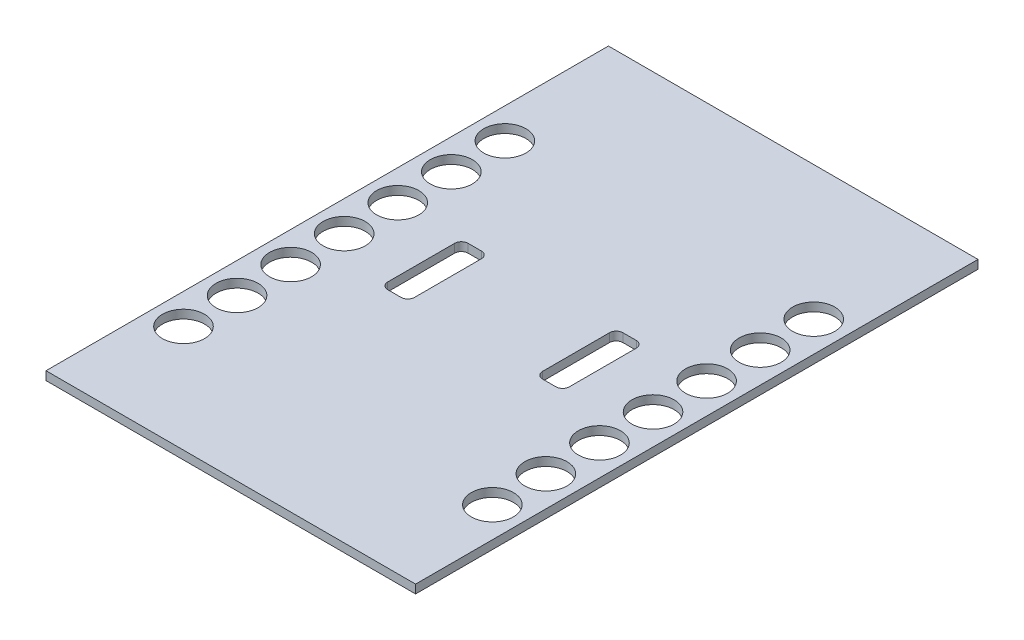
SolidWorks part; units mm, degrees
material "6061-T6 (SS)"
ref_plane "Front Plane" through (0, 0, 0) normal (0, 0, 1) x (1, 0, 0)
ref_plane "Top Plane" through (0, 0, 0) normal (0, 1, 0) x (1, 0, 0)
ref_plane "Right Plane" through (0, 0, 0) normal (1, 0, 0) x (0, 0, -1)
sketch "Sketch1" plane through (0, 0, 0) normal (0, 1, 0) x (1, 0, 0)
  line L1 (-87.63, 133.35) -> (87.63, 133.35)
  line L2 (-87.63, 133.35) -> (-87.63, -133.35)
  line L3 (-87.63, -133.35) -> (87.63, -133.35)
  line L4 (87.63, 133.35) -> (87.63, -133.35)
  line L5 (-87.63, 133.35) -> (87.63, -133.35) construction
  line L6 (-87.63, -133.35) -> (87.63, 133.35) construction
  point P0 (0, 0)
  dimension "D1" = 175.26
  dimension "D2" = 266.7
extrude "Boss-Extrude1" add sketch "Sketch1" along normal blind 4.064
sketch "Sketch2" plane through (0, 4.064, 0) normal (0, 1, 0) x (1, 0, 0)
  line L0 (-87.63, 133.35) -> (-87.63, -133.35) construction
  line L1 (-43.0665, 19.05) -> (-30.3665, 19.05)
  line L2 (-43.0665, 19.05) -> (-43.0665, -19.05)
  line L3 (-43.0665, -19.05) -> (-30.3665, -19.05)
  line L4 (-30.3665, 19.05) -> (-30.3665, -19.05)
  line L5 (-43.0665, 19.05) -> (-30.3665, -19.05) construction
  line L6 (-43.0665, -19.05) -> (-30.3665, 19.05) construction
  point P0 (-36.7165, 0)
  point P7 (0, 0)
  dimension "D1" = 50.9135
  dimension "D2" = 12.7
  dimension "D3" = 38.1
extrude "Cut-Extrude1" cut sketch "Sketch2" against normal through all
mirror "Mirror1" about plane through (0, 0, 0) normal (1, 0, 0) of "Cut-Extrude1"
fillet "Fillet1" radius 3.175 8 edges at (43.0665, 2.032, 19.05) (30.3665, 2.032, 19.05) (43.0665, 2.032, -19.05) (30.3665, 2.032, -19.05) (-30.3665, 2.032, 19.05) (-43.0665, 2.032, 19.05) (-30.3665, 2.032, -19.05) (-43.0665, 2.032, -19.05)
sketch "Sketch3" plane through (0, 4.064, 0) normal (0, 1, 0) x (1, 0, 0)
  line L0 (-87.63, 133.35) -> (-87.63, -133.35) construction
  line L2 (-87.63, -133.35) -> (87.63, -133.35) construction
  circle A0 centre (-73.23, 69.85) radius 10
  circle A1 centre (-73.23, 44.45) radius 10
  circle A2 centre (-73.23, 19.05) radius 10
  circle A3 centre (-73.23, -6.35) radius 10
  circle A4 centre (-73.23, -31.75) radius 10
  circle A5 centre (-73.23, -57.15) radius 10
  circle A6 centre (-73.23, -82.55) radius 10
  point P7 (-73.23, -62.7255)
  dimension "D1" = 20
  dimension "D2" = 14.4
  dimension "D3" = 50.8
  dimension "D5" = 25.4
  dimension "D4" = 7
extrude "Cut-Extrude2" cut sketch "Sketch3" against normal through all
mirror "Mirror2" about plane through (0, 0, 0) normal (1, 0, 0) of "Cut-Extrude2"
